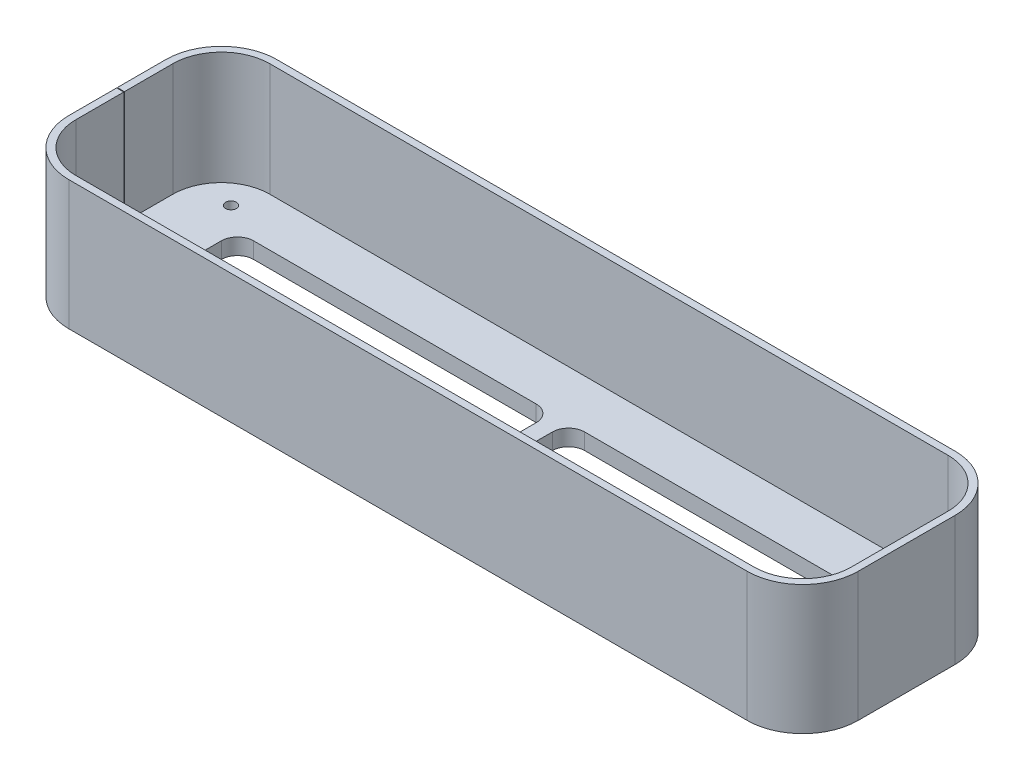
SolidWorks part; units mm, degrees
material "Acrylic (Medium-high impact)"
ref_plane "Front" through (0, 0, 0) normal (0, 0, 1) x (1, 0, 0)
ref_plane "Top" through (0, 0, 0) normal (0, 1, 0) x (1, 0, 0)
ref_plane "Right" through (0, 0, 0) normal (1, 0, 0) x (0, 0, -1)
sketch "Sketch1" plane through (0, 0, 0) normal (0, 1, 0) x (1, 0, 0)
  line L1 (-152.4, 38.1) -> (152.4, 38.1)
  line L2 (-152.4, 38.1) -> (-152.4, -38.1)
  line L3 (-152.4, -38.1) -> (152.4, -38.1)
  line L4 (152.4, 38.1) -> (152.4, -38.1)
  line L5 (-152.4, 38.1) -> (152.4, -38.1) construction
  line L6 (-152.4, -38.1) -> (152.4, 38.1) construction
  point P0 (0, 0)
  dimension "D1" = 304.8
  dimension "D2" = 76.2
extrude "Boss-Extrude1" add sketch "Sketch1" along normal blind 6.35
sketch "Sketch2" plane through (0, 6.35, 0) normal (0, 1, 0) x (1, 0, 0)
  line L0 (152.4, -38.1) -> (152.4, 38.1) construction
  line L1 (-127, 19.05) -> (127, 19.05)
  line L2 (-127, 19.05) -> (-127, -19.05)
  line L3 (-127, -19.05) -> (127, -19.05)
  line L4 (127, 19.05) -> (127, -19.05)
  line L5 (-127, 19.05) -> (127, -19.05) construction
  line L6 (-127, -19.05) -> (127, 19.05) construction
  point P0 (0, 0)
  point P6 (127, 0)
  dimension "D1" = 38.1
  dimension "D2" = 25.4
extrude "Cut-Extrude1" cut sketch "Sketch2" against normal through all
sketch "Sketch3" plane through (0, 6.35, 0) normal (0, 1, 0) x (1, 0, 0)
  line L0 (-127, -19.05) -> (127, -19.05) construction
  line L1 (-3.175, 19.05) -> (3.175, 19.05)
  line L2 (-3.175, 19.05) -> (-3.175, -19.05)
  line L3 (-3.175, -19.05) -> (3.175, -19.05)
  line L4 (3.175, 19.05) -> (3.175, -19.05)
  line L5 (-3.175, 19.05) -> (3.175, -19.05) construction
  line L6 (-3.175, -19.05) -> (3.175, 19.05) construction
  point P0 (0, 0)
  dimension "D1" = 6.35
extrude "Boss-Extrude2" add sketch "Sketch3" against normal up to surface (6.35 mm away) up to face at (0, 0, 0)
fillet "Fillet1" radius 19.05 4 edges at (152.4, 3.175, -38.1) (152.4, 3.175, 38.1) (-152.4, 3.175, 38.1) (-152.4, 3.175, -38.1)
fillet "Fillet2" radius 6.35 8 edges at (3.175, 3.175, 19.05) (3.175, 3.175, -19.05) (127, 3.175, -19.05) (127, 3.175, 19.05) (-3.175, 3.175, 19.05) (-3.175, 3.175, -19.05) (-127, 3.175, -19.05) (-127, 3.175, 19.05)
sketch "Sketch4" plane through (0, 6.35, 0) normal (0, 1, 0) x (1, 0, 0)
  line L0 (133.35, 38.1) -> (-133.35, 38.1) construction
  line L1 (-137.16, 26.67) -> (137.16, 26.67) construction
  line L2 (-137.16, 26.67) -> (-137.16, -26.67) construction
  line L3 (-137.16, -26.67) -> (137.16, -26.67) construction
  line L4 (137.16, 26.67) -> (137.16, -26.67) construction
  line L5 (-137.16, 26.67) -> (137.16, -26.67) construction
  line L6 (-137.16, -26.67) -> (137.16, 26.67) construction
  line L7 (152.4, -19.05) -> (152.4, 19.05) construction
  circle A0 centre (137.16, 26.67) radius 2.14
  circle A1 centre (137.16, -26.67) radius 2.14
  circle A2 centre (-137.16, -26.67) radius 2.14
  circle A3 centre (-137.16, 26.67) radius 2.14
  point P0 (0, 0)
  dimension "D3" = 4.2799
  dimension "D1" = 11.43
  dimension "D2" = 15.24
extrude "Cut-Extrude2" cut sketch "Sketch4" against normal through all
sketch "Sketch5" plane through (0, 0, 0) normal (0, 1, 0) x (1, 0, 0)
  line L0 (-155.194, 19.05) -> (-155.194, 0)
  line L1 (-133.35, -40.894) -> (133.35, -40.894)
  line L2 (155.194, -19.05) -> (155.194, 19.05)
  line L3 (133.35, 40.894) -> (-133.35, 40.894)
  line L4 (152.4, -19.05) -> (152.4, 19.05)
  line L5 (133.35, 38.1) -> (-133.35, 38.1)
  line L6 (-152.4, 19.05) -> (-152.4, -19.05)
  line L7 (-133.35, -38.1) -> (133.35, -38.1)
  line L8 (152.4, -19.05) -> (152.4, 19.05)
  line L9 (133.35, 38.1) -> (-133.35, 38.1)
  line L10 (-152.4, 19.05) -> (-152.4, 0)
  line L11 (-133.35, -38.1) -> (133.35, -38.1)
  line L12 (-152.4, 0) -> (-155.194, 0)
  line L13 (-152.4, -0.254) -> (-155.194, -0.254)
  line L14 (-155.194, -0.254) -> (-155.194, -19.05)
  line L15 (-155.194, 19.05) -> (-155.194, -19.05) construction
  line L16 (-152.4, -0.254) -> (-152.4, -19.05)
  line L17 (-152.4, 19.05) -> (-152.4, -19.05) construction
  arc A0 (-133.35, 40.894) -> (-155.194, 19.05) centre (-133.35, 19.05) ccw
  arc A1 (-155.194, -19.05) -> (-133.35, -40.894) centre (-133.35, -19.05) ccw
  arc A2 (133.35, -40.894) -> (155.194, -19.05) centre (133.35, -19.05) ccw
  arc A3 (155.194, 19.05) -> (133.35, 40.894) centre (133.35, 19.05) ccw
  arc A4 (152.4, 19.05) -> (133.35, 38.1) centre (133.35, 19.05) ccw
  arc A5 (-133.35, 38.1) -> (-152.4, 19.05) centre (-133.35, 19.05) ccw
  arc A6 (-152.4, -19.05) -> (-133.35, -38.1) centre (-133.35, -19.05) ccw
  arc A7 (133.35, -38.1) -> (152.4, -19.05) centre (133.35, -19.05) ccw
  arc A8 (152.4, 19.05) -> (133.35, 38.1) centre (133.35, 19.05) ccw
  arc A9 (-133.35, 38.1) -> (-152.4, 19.05) centre (-133.35, 19.05) ccw
  arc A10 (-152.4, -19.05) -> (-133.35, -38.1) centre (-133.35, -19.05) ccw
  arc A11 (133.35, -38.1) -> (152.4, -19.05) centre (133.35, -19.05) ccw
  dimension "D3" = 0.254
  dimension "D4" = 38.1
  dimension "D1" = 0
  dimension "D2" = 2.794
extrude "Boss-Extrude3" add sketch "Sketch5" along normal blind 50.8 separate body
